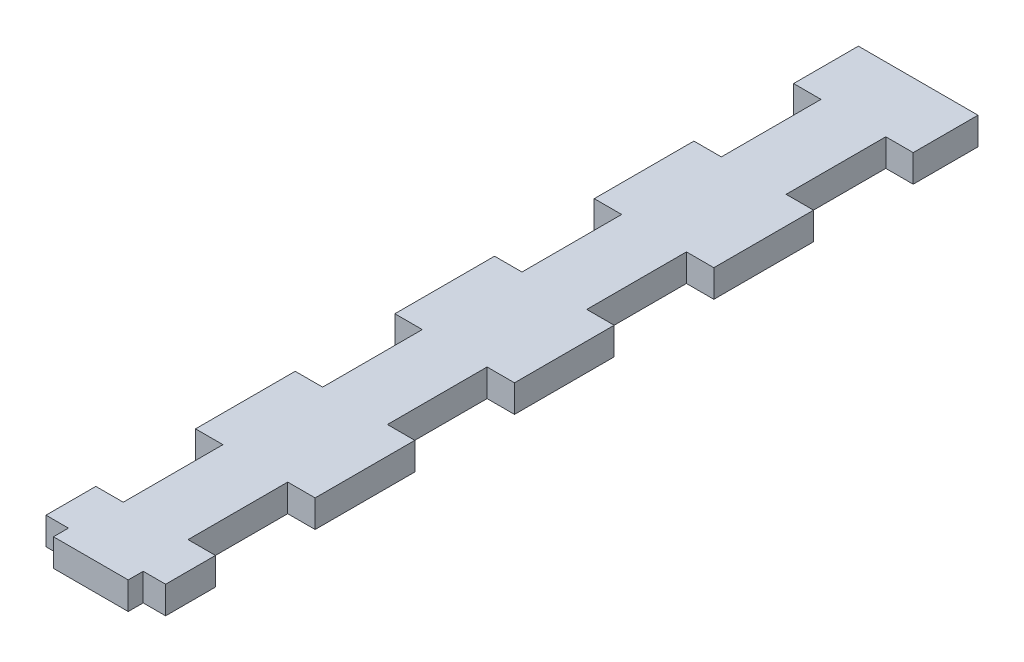
SolidWorks part; units mm, degrees
ref_plane "Alzado" through (0, 0, 0) normal (0, 0, 1) x (1, 0, 0)
ref_plane "Planta" through (0, 0, 0) normal (0, 1, 0) x (1, 0, 0)
ref_plane "Vista lateral" through (0, 0, 0) normal (1, 0, 0) x (0, 0, -1)
sketch "Croquis1" plane through (0, 0, 0) normal (0, 1, 0) x (1, 0, 0)
  line L0 (4.5, 0) -> (19.5, 0)
  line L1 (24, 3) -> (24, 13)
  line L2 (24, 166) -> (0, 166)
  line L3 (0, 166) -> (0, 153)
  line L4 (12, 0) -> (19.5, 0)
  line L5 (0, 83) -> (0, 93)
  line L6 (0, 93) -> (5.5, 93)
  line L7 (5.5, 93) -> (5.5, 113)
  line L8 (5.5, 113) -> (0, 113)
  line L9 (0, 113) -> (0, 133)
  line L10 (0, 133) -> (5.5, 133)
  line L11 (5.5, 133) -> (5.5, 153)
  line L12 (5.5, 153) -> (0, 153)
  line L13 (5.5, 13) -> (0, 13)
  line L14 (5.5, 33) -> (5.5, 13)
  line L15 (0, 33) -> (5.5, 33)
  line L16 (5.5, 53) -> (0, 53)
  line L17 (5.5, 73) -> (5.5, 53)
  line L18 (0, 73) -> (5.5, 73)
  line L19 (24, 73) -> (18.5, 73)
  line L20 (18.5, 73) -> (18.5, 53)
  line L21 (18.5, 53) -> (24, 53)
  line L22 (24, 33) -> (18.5, 33)
  line L23 (18.5, 33) -> (18.5, 13)
  line L24 (18.5, 13) -> (24, 13)
  line L25 (18.5, 153) -> (24, 153)
  line L26 (18.5, 133) -> (18.5, 153)
  line L27 (24, 133) -> (18.5, 133)
  line L28 (18.5, 113) -> (24, 113)
  line L29 (18.5, 93) -> (18.5, 113)
  line L30 (24, 93) -> (18.5, 93)
  line L31 (19.5, 0) -> (19.5, 3)
  line L32 (19.5, 3) -> (24, 3)
  line L33 (12, 0) -> (4.5, 0)
  line L34 (4.5, 0) -> (4.5, 3)
  line L35 (4.5, 3) -> (0, 3)
  line L36 (0, 13) -> (0, 3)
  line L37 (0, 53) -> (0, 33)
  line L38 (0, 93) -> (0, 73)
  line L39 (0, 133) -> (0, 113)
  line L40 (24, 153) -> (24, 166)
  line L41 (24, 113) -> (24, 133)
  line L42 (24, 73) -> (24, 93)
  line L43 (24, 33) -> (24, 53)
  dimension "D3" = 7.5
  dimension "D4" = 10
  dimension "D5" = 20
  dimension "D6" = 20
  dimension "D7" = 20
  dimension "D8" = 3
extrude "Saliente-Extruir1" add sketch "Croquis1" along normal blind 5.5 contours L22 L43 L21 L20 L19 L42 L30 L29 L28 L41 L27 L26 L25 L40 L2 L3 L12 L11 L10 L9 L8 L7 L6 L5 L38 L18 L17 L16 L37 L15 L14 L13 L36 L35 L34 L0 L31 L32 L1 L24 L23 region at (12, 0, -83.7151)
